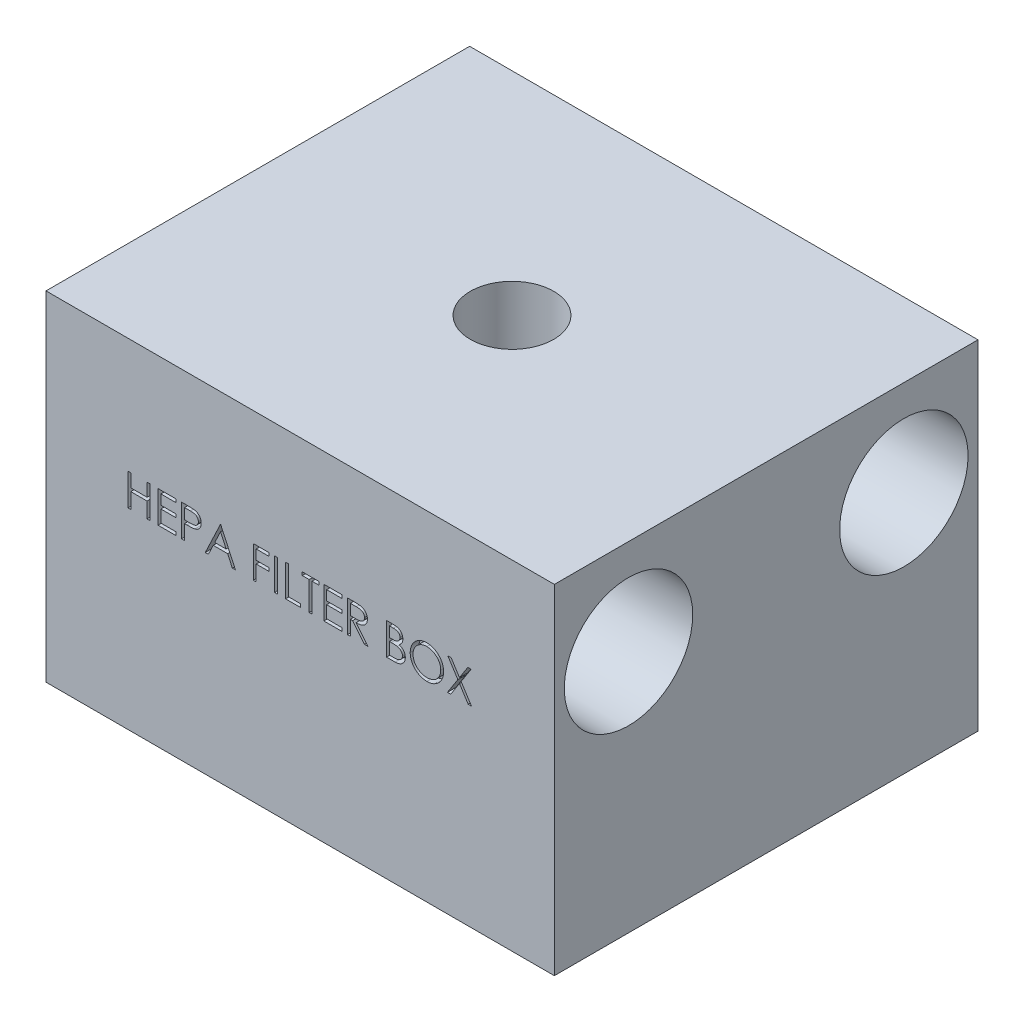
SolidWorks part; units mm, degrees
ref_plane "Front" through (0, 0, 0) normal (0, 0, 1) x (1, 0, 0)
ref_plane "Top" through (0, 0, 0) normal (0, 1, 0) x (1, 0, 0)
ref_plane "Right" through (0, 0, 0) normal (1, 0, 0) x (0, 0, -1)
ref_axis "Axis1" through (0, 0, 55) along (0, 0, -1)
sketch "Sketch1" plane through (0, 0, 0) normal (0, 1, 0) x (1, 0, 0)
  line L1 (-76.2, 63.5) -> (76.2, 63.5)
  line L2 (-76.2, 63.5) -> (-76.2, -63.5)
  line L3 (-76.2, -63.5) -> (76.2, -63.5)
  line L4 (76.2, 63.5) -> (76.2, -63.5)
  line L5 (-76.2, 63.5) -> (76.2, -63.5) construction
  line L6 (-76.2, -63.5) -> (76.2, 63.5) construction
  point P0 (0, 0)
  dimension "D1" = 152.4
  dimension "D2" = 127
extrude "Boss-Extrude1" add sketch "Sketch1" along normal blind 101.6
sketch "Sketch2" plane through (76.2, 0, 0) normal (1, 0, 0) x (0, 0, -1)
  line L0 (-41.275, 73.025) -> (41.275, 73.025) construction
  line L1 (0, 0) -> (0, 101.6) construction
  line L2 (-63.5, 0) -> (63.5, 0) construction
  line L3 (-63.5, 101.6) -> (63.5, 101.6) construction
  circle A0 centre (-41.275, 73.025) radius 19.25
  circle A1 centre (41.275, 73.025) radius 19.25
  point P10 (0, 73.025)
  dimension "D1" = 38.5
  dimension "D2" = 82.55
  dimension "D3" = 73.025
extrude "Cut-Extrude1" cut sketch "Sketch2" against normal blind 50.8
sketch "Sketch3" plane through (0, 101.6, 0) normal (0, 1, 0) x (1, 0, 0)
  line L0 (-76.2, 0) -> (76.2, 0) construction
  line L1 (-76.2, 63.5) -> (-76.2, -63.5) construction
  line L2 (76.2, -63.5) -> (76.2, 63.5) construction
  line L3 (0, -63.5) -> (0, 63.5) construction
  line L4 (-76.2, -63.5) -> (76.2, -63.5) construction
  line L5 (76.2, 63.5) -> (-76.2, 63.5) construction
  circle A0 centre (0, 0) radius 12.5
  dimension "D1" = 25
extrude "Cut-Extrude2" cut sketch "Sketch3" against normal blind 50.8
sketch "Sketch4" plane through (0, 0, 63.5) normal (0, 0, 1) x (1, 0, 0)
  text T0 "HEPA FILTER BOX" font "Century Gothic" height in points 36
extrude "Cut-Extrude3" cut sketch "Sketch4" against normal blind 2.54
